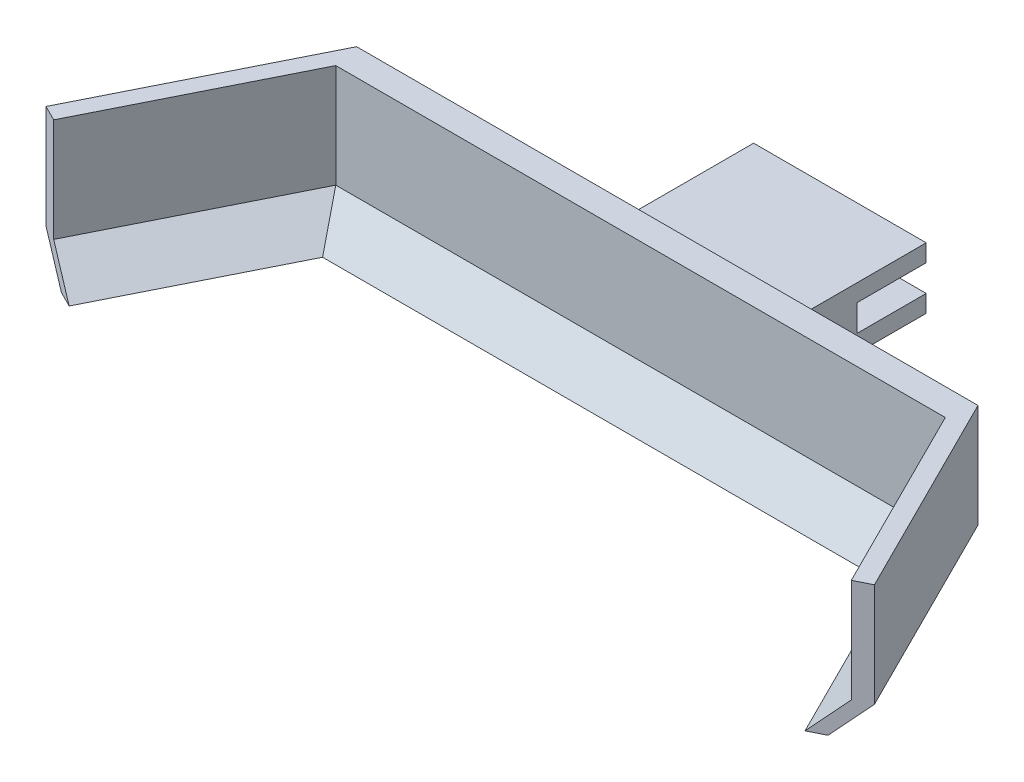
SolidWorks part; units mm, degrees
ref_plane "Front Plane" through (0, 0, 0) normal (0, 0, 1) x (1, 0, 0)
ref_plane "Top Plane" through (0, 0, 0) normal (0, 1, 0) x (1, 0, 0)
ref_plane "Right Plane" through (0, 0, 0) normal (1, 0, 0) x (0, 0, -1)
sketch "Sketch2" plane through (0, 0, 0) normal (0, 1, 0) x (1, 0, 0)
  line L0 (90, 5) -> (120, 5) construction
  line L1 (-90, 5) -> (90, 5)
  line L7 (-90, 5) -> (-120, 5) construction
  line L8 (-120, 5) -> (-120, -55) construction
  line L9 (-90, 5) -> (-120, -55)
  line L10 (-88.2918, -2.7639) -> (-115.5279, -57.2361)
  line L11 (-120, -55) -> (-115.5279, -57.2361)
  line L12 (-88.2918, -2.7639) -> (88.2918, -2.7639)
  line L13 (-85.5279, 2.7639) -> (-115.5279, -57.2361) construction
  line L14 (120, 5) -> (120, -55) construction
  line L15 (90, 5) -> (120, -55)
  line L16 (88.2918, -2.7639) -> (115.5279, -57.2361)
  line L17 (115.5279, -57.2361) -> (120, -55)
  line L18 (85.5279, 2.7639) -> (115.5279, -57.2361) construction
  point P0 (0, 0)
  dimension "D1" = 180
  dimension "D3" = 30
  dimension "D4" = 30
  dimension "D5" = 60
  dimension "D7" = 60
  dimension "D6" = 5
  dimension "D8" = 5
extrude "Boss-Extrude1" add sketch "Sketch2" along normal blind 10
draft "Draft1" type of draft neutral plane draft angle 45 faces to draft 3 face at (101.9098, 5, 30) face at (0, 5, 2.7639) face at (-101.9098, 5, 30) neutral plane through (0, 10, 0) neutral plane normal (0, 1, 0) parameters "D1"=45
sketch "Sketch5" plane through (0, 10, 0) normal (0, 1, 0) x (1, 0, 0)
  line L0 (-120, -55) -> (-90, 5)
  line L1 (-90, 5) -> (90, 5)
  line L2 (90, 5) -> (120, -55)
  line L3 (120, -55) -> (115.5279, -57.2361)
  line L4 (115.5279, -57.2361) -> (88.2918, -2.7639)
  line L5 (88.2918, -2.7639) -> (-88.2918, -2.7639)
  line L6 (-88.2918, -2.7639) -> (-115.5279, -57.2361)
  line L7 (-115.5279, -57.2361) -> (-120, -55)
extrude "Boss-Extrude2" add sketch "Sketch5" along normal blind 30
sketch "Sketch6" plane through (0, 0, -5) normal (0, 0, -1) x (-1, 0, 0)
  line L0 (0, 0) -> (0, 14.45) construction
  line L2 (-25, 5.6) -> (25, 5.6)
  line L3 (-25, 5.6) -> (-25, 23.3)
  line L4 (-25, 23.3) -> (25, 23.3)
  line L5 (25, 5.6) -> (25, 23.3)
  line L6 (-25, 5.6) -> (25, 23.3) construction
  line L7 (-25, 23.3) -> (25, 5.6) construction
  point P5 (0, 14.45)
  dimension "D1" = 50
  dimension "D2" = 17.7
  dimension "D3" = 14.45
extrude "Boss-Extrude3" add sketch "Sketch6" along normal blind 50
sketch "Sketch7" plane through (0, 0, -55) normal (0, 0, -1) x (-1, 0, 0)
  line L0 (-25, 5.6) -> (-25, 10.6) construction
  line L1 (-25, 23.3) -> (-25, 5.6) construction
  line L2 (25, 5.6) -> (25, 23.3) construction
  line L3 (-25, 10.6) -> (25, 10.6)
  line L4 (-25, 10.6) -> (-25, 18.3)
  line L5 (-25, 18.3) -> (25, 18.3)
  line L6 (25, 10.6) -> (25, 18.3)
  dimension "D1" = 5
  dimension "D2" = 7.7
extrude "Cut-Extrude4" cut sketch "Sketch7" against normal blind 20
chamfer "Chamfer1" distance 10 angle 45 3 edges at (105, 0, 25) (0, 0, -5) (-105, 0, 25)
